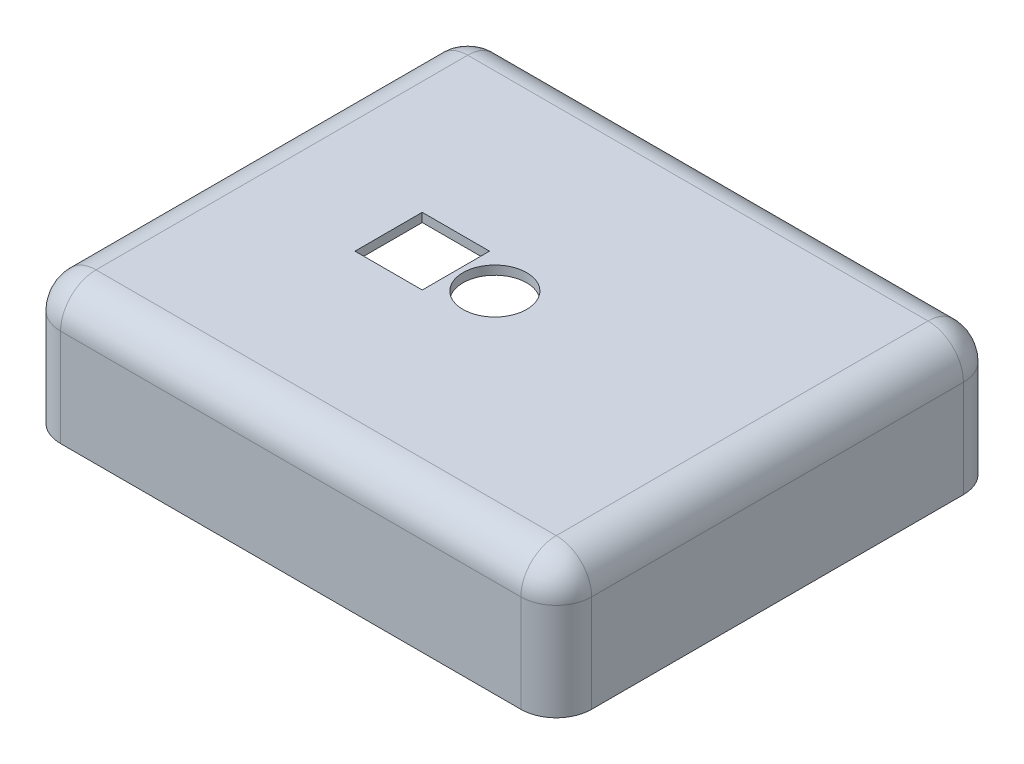
SolidWorks part; units mm, degrees
ref_plane "Front Plane" through (0, 0, 0) normal (0, 0, 1) x (1, 0, 0)
ref_plane "Top Plane" through (0, 0, 0) normal (0, 1, 0) x (1, 0, 0)
ref_plane "Right Plane" through (0, 0, 0) normal (1, 0, 0) x (0, 0, -1)
sketch "Sketch2" plane through (0, 0, 0) normal (0, 1, 0) x (1, 0, 0)
  line L1 (0, 0) -> (76.2, 0)
  line L2 (0, 0) -> (0, 63.5)
  line L3 (0, 63.5) -> (76.2, 63.5)
  line L4 (76.2, 0) -> (76.2, 63.5)
  line L5 (7.112, 53.34) -> (42.672, 53.34)
  line L6 (7.112, 53.34) -> (7.112, 9.22)
  line L7 (7.112, 9.22) -> (42.672, 9.22)
  line L8 (42.672, 53.34) -> (42.672, 9.22)
  line L9 (43.942, 55.448) -> (69.85, 55.448)
  line L10 (43.942, 55.448) -> (43.942, 6.68)
  line L11 (43.942, 6.68) -> (69.85, 6.68)
  line L12 (69.85, 55.448) -> (69.85, 6.68)
  line L13 (22.352, 34.62) -> (29.972, 34.62)
  line L14 (22.352, 34.62) -> (22.352, 27)
  line L15 (22.352, 27) -> (29.972, 27)
  line L16 (29.972, 34.62) -> (29.972, 27)
  line L17 (21.336, 35.636) -> (30.988, 35.636)
  line L18 (21.336, 35.636) -> (21.336, 25.984)
  line L19 (21.336, 25.984) -> (30.988, 25.984)
  line L20 (30.988, 35.636) -> (30.988, 25.984)
  circle A0 centre (36.322, 31.064) radius 3.81
  circle A1 centre (36.322, 31.064) radius 4.572
  point P13 (69.85, 31.064)
  dimension "D15" = 7.62
  dimension "D22" = 9.144
  dimension "D1" = 76.2
  dimension "D2" = 63.5
  dimension "D3" = 35.56
  dimension "D4" = 44.12
  dimension "D5" = 1.27
  dimension "D6" = 10.16
  dimension "D7" = 25.908
  dimension "D8" = 48.768
  dimension "D9" = 2.54
  dimension "D10" = 6.35
  dimension "D11" = 25.4
  dimension "D12" = 7.62
  dimension "D13" = 7.62
  dimension "D14" = 21.844
  dimension "D16" = 13.97
  dimension "D17" = 20.32
  dimension "D18" = 1.016
  dimension "D19" = 1.016
  dimension "D20" = 1.016
  dimension "D21" = 1.016
extrude "Boss-Extrude1" add sketch "Sketch2" along normal blind 0.0003 and the other way blind 19.05 contours L3 L4 L1 L2
sketch "Sketch3" plane through (0, -19.05, 0) normal (0, -1, 0) x (-1, 0, 0)
  line L0 (0, 63.5) -> (-76.2, 63.5) construction
  line L1 (-73.66, 60.96) -> (-2.54, 60.96)
  line L2 (-73.66, 60.96) -> (-73.66, 2.54)
  line L3 (-73.66, 2.54) -> (-2.54, 2.54)
  line L4 (-2.54, 60.96) -> (-2.54, 2.54)
  line L5 (0, 0) -> (-76.2, 0) construction
  line L6 (-76.2, 0) -> (-76.2, 63.5) construction
  line L7 (0, 0) -> (0, 63.5) construction
  dimension "D1" = 2.54
  dimension "D2" = 2.54
  dimension "D3" = 2.54
  dimension "D4" = 2.54
extrude "Cut-Extrude2" cut sketch "Sketch3" against normal blind 17.78
extrude "Cut-Extrude3" cut sketch "Sketch2<3>" against normal through all and the other way blind 2.54 contours L17 L20 L19 L18 | A1
sketch "Sketch2<3>" plane through (0, 0, 0) normal (0, 1, 0) x (1, 0, 0) same geometry as "Sketch2"
fillet "Fillet1" radius 5.08 1 edges at (76.2, -9.5249, -63.5)
fillet "Fillet2" radius 5.08 1 edges at (73.66, -10.16, -60.96)
fillet "Fillet3" radius 5.08 2 edges at (76.2, -9.5249, 0) (73.66, -10.16, -2.54)
fillet "Fillet4" radius 5.08 2 edges at (0, -9.5249, 0) (2.54, -10.16, -2.54)
fillet "Fillet5" radius 5.08 2 edges at (0, -9.5249, -63.5) (2.54, -10.16, -60.96)
fillet "Fillet6" radius 5.08 8 edges at (1.4879, 0.0003, -1.4879) (38.1, 0.0003, 0) (74.7121, 0.0003, -1.4879) (76.2, 0.0003, -31.75) (74.7121, 0.0003, -62.0121) (38.1, 0.0003, -63.5) (1.4879, 0.0003, -62.0121) (0, 0.0003, -31.75)
sketch "Sketch5" plane through (0, -19.05, 0) normal (0, -1, 0) x (1, 0, 0)
  line L8 (1.27, -7.62) -> (1.27, -55.88)
  line L9 (68.58, -1.27) -> (7.62, -1.27)
  line L10 (74.93, -55.88) -> (74.93, -7.62)
  line L11 (7.62, -62.23) -> (68.58, -62.23)
  line L12 (1.27, -7.62) -> (1.27, -55.88)
  line L13 (68.58, -1.27) -> (7.62, -1.27)
  line L14 (74.93, -55.88) -> (74.93, -7.62)
  line L15 (7.62, -62.23) -> (68.58, -62.23)
  arc A8 (1.27, -55.88) -> (7.62, -62.23) centre (7.62, -55.88) ccw
  arc A9 (7.62, -1.27) -> (1.27, -7.62) centre (7.62, -7.62) ccw
  arc A10 (74.93, -7.62) -> (68.58, -1.27) centre (68.58, -7.62) ccw
  arc A11 (68.58, -62.23) -> (74.93, -55.88) centre (68.58, -55.88) ccw
  arc A12 (1.27, -55.88) -> (7.62, -62.23) centre (7.62, -55.88) ccw
  arc A13 (7.62, -1.27) -> (1.27, -7.62) centre (7.62, -7.62) ccw
  arc A14 (74.93, -7.62) -> (68.58, -1.27) centre (68.58, -7.62) ccw
  arc A15 (68.58, -62.23) -> (74.93, -55.88) centre (68.58, -55.88) ccw
  dimension "D1" = 1.27
extrude "Cut-Extrude4" cut sketch "Sketch5" against normal blind 5.08
